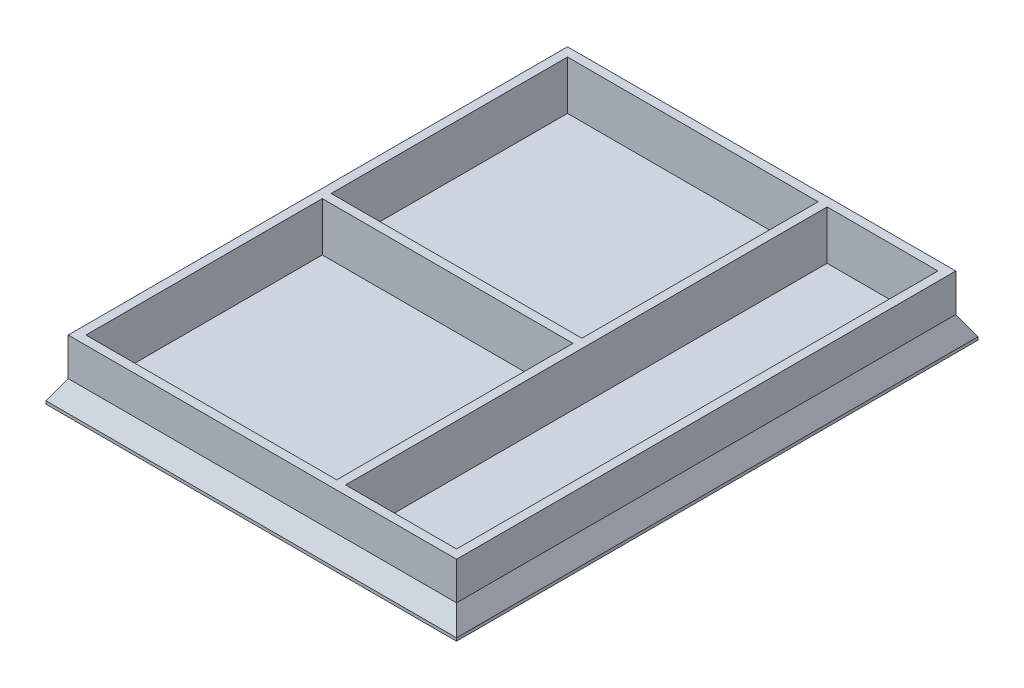
SolidWorks part; units mm, degrees
ref_plane "Přední rovina" through (0, 0, 0) normal (0, 0, 1) x (1, 0, 0)
ref_plane "Horní rovina" through (0, 0, 0) normal (0, 1, 0) x (1, 0, 0)
ref_plane "Pravá rovina" through (0, 0, 0) normal (1, 0, 0) x (0, 0, -1)
sketch "Skica1" plane through (0, 0, 0) normal (0, 1, 0) x (1, 0, 0)
  line L0 (-74, 94) -> (0, 0) construction
  line L1 (0, 0) -> (-74, 0)
  line L2 (0, 0) -> (0, 94)
  line L3 (0, 94) -> (-74, 94)
  line L4 (-74, 0) -> (-74, 94)
  line L5 (-74, 0) -> (0, 94) construction
  line L7 (-72, 92) -> (-2, 92)
  line L8 (-72, 92) -> (-72, 2)
  line L9 (-72, 2) -> (-2, 2)
  line L10 (-2, 92) -> (-2, 2)
  line L11 (-72, 92) -> (-2, 2) construction
  line L12 (-72, 2) -> (-2, 92) construction
  line L13 (-72, 47) -> (-2, 47) construction
  line L15 (-23.6, 90.4) -> (-3.6, 90.4)
  line L16 (-23.6, 90.4) -> (-23.6, 3.6)
  line L17 (-23.6, 3.6) -> (-3.6, 3.6)
  line L18 (-3.6, 90.4) -> (-3.6, 3.6)
  line L19 (-70.4, 90.4) -> (-25.2, 90.4)
  line L20 (-70.4, 90.4) -> (-70.4, 47.8)
  line L21 (-70.4, 47.8) -> (-25.2, 47.8)
  line L22 (-25.2, 90.4) -> (-25.2, 47.8)
  line L23 (-70.4, 46.2) -> (-25.2, 46.2)
  line L24 (-70.4, 46.2) -> (-70.4, 3.6)
  line L25 (-70.4, 3.6) -> (-25.2, 3.6)
  line L26 (-25.2, 46.2) -> (-25.2, 3.6)
  point P4 (-37, 47)
  dimension "D1" = 74
  dimension "D2" = 94
  dimension "D3" = 70
  dimension "D4" = 90
  dimension "D5" = 1.6
  dimension "D6" = 1.6
  dimension "D7" = 1.6
  dimension "D8" = 1.6
  dimension "D9" = 1.6
  dimension "D10" = 1.6
  dimension "D11" = 0.8
  dimension "D12" = 0.8
  dimension "D13" = 1.6
  dimension "D14" = 20
  dimension "D15" = 1.6
  dimension "D16" = 1.6
extrude "Přidat vysunutím1" add sketch "Skica1" along normal blind 2 contours L3 L4 L1 L2
extrude "Přidat vysunutím2" add sketch "Skica1<3>" along normal blind 10.8 contours L10 L7 L8 L9 L15 L18 L17 L16 L19 L22 L21 L20 L23 L26 L25 L24 region at (-35.6411, 0, -47)
sketch "Skica1<3>" plane through (0, 0, 0) normal (0, 1, 0) x (1, 0, 0) same geometry as "Skica1"
extrude "Přidat vysunutím3" add sketch "Skica1<4>" along normal blind 4 contours L4 L1 L2 L3 L7 L10 L9 L8 region at (-37, 0, -1.1963)
sketch "Skica1<4>" plane through (0, 0, 0) normal (0, 1, 0) x (1, 0, 0) same geometry as "Skica1"
chamfer "Zkosení2" distance 2 angle 60 4 edges at (-74, 4, -47) (-37, 4, -94) (0, 4, -47) (-37, 4, 0) first distance on face at (-37, 4, -47)
